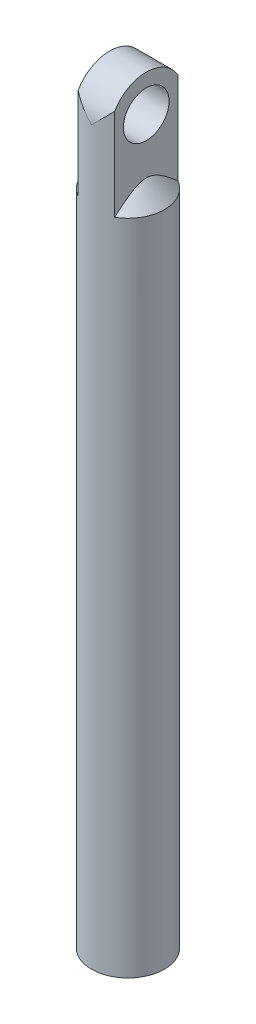
SolidWorks part; units mm, degrees
material "AISI 1020"
ref_plane "Front" through (0, 0, 0) normal (0, 0, 1) x (1, 0, 0)
ref_plane "Top" through (0, 0, 0) normal (0, 1, 0) x (1, 0, 0)
ref_plane "Right" through (0, 0, 0) normal (1, 0, 0) x (0, 0, -1)
sketch "Sketch1" plane through (0, 0, 0) normal (0, 1, 0) x (1, 0, 0)
  circle A0 centre (0, 0) radius 4
  dimension "D1" = 8
extrude "Boss-Extrude1" add sketch "Sketch1" along normal blind 55 contours A0
sketch "Sketch2" plane through (0, 0, 0) normal (1, 0, 0) x (0, 0, -1)
  line L0 (4, 55) -> (-4, 55) construction
  line L2 (-4, 60.0339) -> (-4, 55)
  line L3 (-4, 55) -> (4, 55)
  line L4 (4, 60.0339) -> (4, 55)
  line L5 (4, 0) -> (4, 55) construction
  line L7 (-4, 55) -> (-4, 0) construction
  arc A0 (4, 60.0339) -> (-4, 60.0339) centre (0, 60.0339) ccw
  circle A1 centre (0, 60.0339) radius 2.5
  dimension "D1" = 5
extrude "Boss-Extrude2" add sketch "Sketch2" along normal blind 2 and the other way blind 2
sketch "Sketch3" plane through (0, 55, 0) normal (0, -1, 0) x (1, 0, 0)
  circle A0 centre (0, 0) radius 5.5
  dimension "D1" = 11
extrude "Boss-Extrude3" add sketch "Sketch3" along normal blind 3 contours A0
chamfer "Chamfer1" distance 2 angle 45 1 edges at (0, 52, -5.5)
sketch "Sketch4" plane through (0, 0, 0) normal (0, -1, 0) x (1, 0, 0)
  circle A0 centre (0, 0) radius 4
extrude "Boss-Extrude4" add sketch "Sketch4" along normal blind 20 contours A0
sketch "Sketch5" plane through (0, -20, 0) normal (0, -1, 0) x (1, 0, 0)
  circle A0 centre (0, 0) radius 4
extrude "Cut-Extrude1" cut sketch "Sketch5" against normal through all flip side to cut
chamfer "Chamfer2" distance 3 angle 45 1 edges at (4, 55, 0)
chamfer "Chamfer3" distance 3 angle 45 1 edges at (-4, 55, 0)
